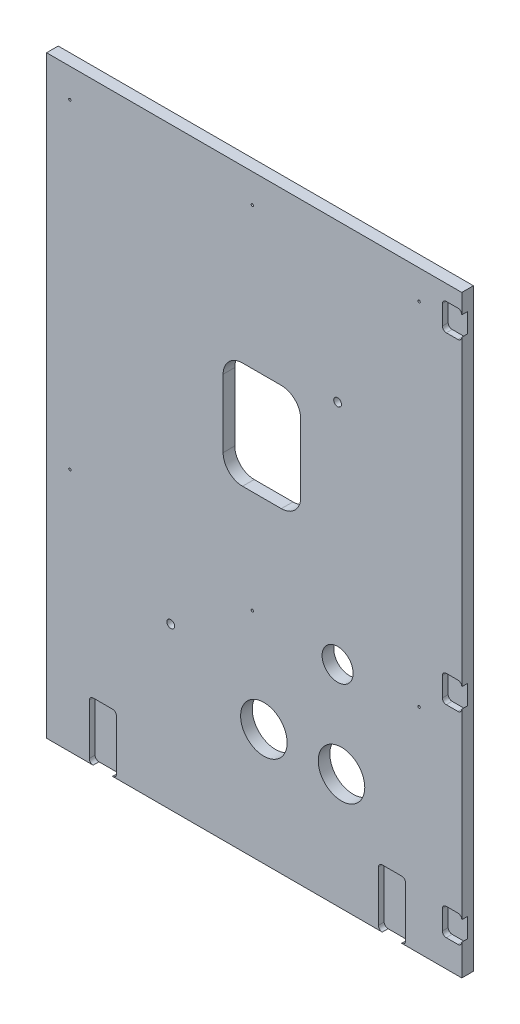
SolidWorks part; units mm, degrees
material "Фанера, берёза, ФСФ ВВ/С ГОСТ 3916.1-96"
ref_plane "Спереди" through (0, 0, 0) normal (0, 0, 1) x (1, 0, 0)
ref_plane "Сверху" through (0, 0, 0) normal (0, 1, 0) x (1, 0, 0)
ref_plane "Справа" through (0, 0, 0) normal (1, 0, 0) x (0, 0, -1)
sketch "Эскиз1" plane through (0, 0, 0) normal (0, 0, 1) x (1, 0, 0)
  line L1 (-535, -765) -> (535, -765)
  line L2 (-535, -765) -> (-535, 765)
  line L3 (-535, 765) -> (535, 765)
  line L4 (535, -765) -> (535, 765)
  line L5 (0, 765) -> (0, -765) construction
  line L6 (-535, 0) -> (535, 0) construction
  point P0 (0, 0)
  dimension "D1" = 1070
  dimension "D2" = 1530
extrude "Бобышка-Вытянуть1" add sketch "Эскиз1" along normal mid plane 30
sketch "Эскиз2" plane through (0, 0, 15) normal (0, 0, 1) x (1, 0, 0)
  line L0 (-535, 765) -> (-535, -765) construction
  line L1 (-30, 325) -> (70, 325)
  line L2 (-80, 275) -> (-80, 100)
  line L3 (-30, 50) -> (70, 50)
  line L4 (120, 275) -> (120, 100)
  line L5 (535, 765) -> (-535, 765) construction
  line L6 (535, -765) -> (535, 765) construction
  line L7 (-535, -765) -> (535, -765) construction
  arc A0 (70, 50) -> (120, 100) centre (70, 100) ccw
  arc A1 (-80, 100) -> (-30, 50) centre (-30, 100) ccw
  arc A2 (70, 325) -> (120, 275) centre (70, 275) cw
  arc A3 (-30, 325) -> (-80, 275) centre (-30, 275) ccw
  circle A4 centre (215, -225) radius 40
  circle A5 centre (225, -465) radius 60
  circle A6 centre (25, -465) radius 60
  circle A7 centre (215, 360) radius 10
  circle A8 centre (-215, -350) radius 10
  point P4 (20, 50)
  dimension "D5" = 50
  dimension "D6" = 80
  dimension "D9" = 120
  dimension "D13" = 20
  dimension "D1" = 275
  dimension "D2" = 200
  dimension "D3" = 455
  dimension "D4" = 440
  dimension "D7" = 320
  dimension "D8" = 540
  dimension "D10" = 310
  dimension "D11" = 300
  dimension "D12" = 510
  dimension "D14" = 405
  dimension "D15" = 320
  dimension "D16" = 320
  dimension "D17" = 415
extrude "Вырез-Вытянуть1" cut sketch "Эскиз2" against normal through all
sketch "Эскиз4" plane through (0, 0, 15) normal (0, 0, 1) x (1, 0, 0)
  line L0 (535, -765) -> (535, 765) construction
  line L1 (535, 765) -> (-535, 765) construction
  line L2 (-535, -765) -> (535, -765) construction
  line L3 (-535, 765) -> (-535, -765) construction
  point P0 (167.9177, -661.5146)
  line B0 (495, -105) -> (525, -105)
  line B1 (485, -115) -> (485, -165)
  line B2 (495, -175) -> (525, -175)
  line B3 (535, -115) -> (535, -165)
  arc B4 (525, -175) -> (535, -165) centre (525, -165) ccw
  arc B5 (485, -165) -> (495, -175) centre (495, -165) ccw
  arc B6 (525, -105) -> (535, -115) centre (525, -115) cw
  arc B7 (495, -105) -> (485, -115) centre (495, -115) ccw
  line B8 (495, -625) -> (525, -625)
  line B9 (485, -635) -> (485, -685)
  line B10 (495, -695) -> (525, -695)
  line B11 (535, -635) -> (535, -685)
  arc B12 (525, -695) -> (535, -685) centre (525, -685) ccw
  arc B13 (485, -685) -> (495, -695) centre (495, -685) ccw
  arc B14 (525, -625) -> (535, -635) centre (525, -635) cw
  arc B15 (495, -625) -> (485, -635) centre (495, -635) ccw
  line B16 (-390, -615) -> (-390, -765) construction
  line B17 (-415, -615) -> (-365, -615)
  line B18 (-425, -625) -> (-425, -755)
  line B19 (-415, -765) -> (-365, -765)
  line B20 (-355, -625) -> (-355, -755)
  arc B21 (-365, -765) -> (-355, -755) centre (-365, -755) ccw
  arc B22 (-425, -755) -> (-415, -765) centre (-415, -755) ccw
  arc B23 (-365, -615) -> (-355, -625) centre (-365, -625) cw
  arc B24 (-415, -615) -> (-425, -625) centre (-415, -625) ccw
  line B25 (495, 725) -> (525, 725)
  line B26 (485, 715) -> (485, 665)
  line B27 (495, 655) -> (525, 655)
  line B28 (535, 715) -> (535, 665)
  arc B29 (525, 655) -> (535, 665) centre (525, 665) ccw
  arc B30 (485, 665) -> (495, 655) centre (495, 665) ccw
  arc B31 (525, 725) -> (535, 715) centre (525, 715) cw
  arc B32 (495, 725) -> (485, 715) centre (495, 715) ccw
  line B33 (330, -615) -> (380, -615)
  line B34 (320, -625) -> (320, -755)
  line B35 (330, -765) -> (380, -765)
  line B36 (390, -625) -> (390, -755)
  arc B37 (380, -765) -> (390, -755) centre (380, -755) ccw
  arc B38 (320, -755) -> (330, -765) centre (330, -755) ccw
  arc B39 (380, -615) -> (390, -625) centre (380, -625) cw
  arc B40 (330, -615) -> (320, -625) centre (330, -625) ccw
  dimension "D1" = 40
  dimension "D2" = 870
  dimension "D3" = 70
  dimension "D4" = 110
  dimension "D5" = 145
sketch_block_instance "Блок1-2"
sketch_block "Блок1" parameters "D3"=10, "D1"=70, "D2"=50
sketch_block_instance "Блок1-3"
sketch_block "Блок1" parameters "D3"=10, "D1"=70, "D2"=50
sketch_block_instance "Блок3-1"
sketch_block "Блок3" parameters "D2"=10, "D1"=70, "D3"=50
sketch_block_instance "Блок1-1"
sketch_block "Блок1" parameters "D3"=10, "D1"=70, "D2"=50
sketch_block_instance "Блок3-2"
extrude "Вырез-Вытянуть2" cut sketch "Эскиз4" against normal blind 15
sketch "Эскиз5" plane through (0, 0, 15) normal (0, 0, 1) x (1, 0, 0)
  line L0 (535, 765) -> (-535, 765) construction
  line L1 (-535, 765) -> (-535, -765) construction
  point P0 (-492.6091, 591.725)
  circle B0 centre (-475, 690) radius 3
  circle B1 centre (-5, 690) radius 3
  circle B2 centre (425, 690) radius 3
  circle B3 centre (-475, -135) radius 3
  circle B4 centre (-5, -215) radius 3
  circle B5 centre (425, -215) radius 3
  dimension "D1" = 75
  dimension "D2" = 60
  dimension "D3" = 470
  dimension "D4" = 430
  dimension "D5" = 825
  dimension "D6" = 905
sketch_block_instance "Блок4-1"
sketch_block "Блок4" parameters "D1"=6
sketch_block_instance "Блок4-2"
sketch_block_instance "Блок4-3"
sketch_block_instance "Блок4-4"
sketch_block_instance "Блок4-5"
sketch_block_instance "Блок4-6"
extrude "Вырез-Вытянуть3" cut sketch "Эскиз5" against normal through all
equation "\"ширина 1-я панель\"=1145"
equation "\"длина панелей\"=1530"
equation "\"толщина дсп\"=30"
equation "\"ширина 2-я панель\"=1070"
equation "\"D2@Эскиз1\"=\"длина панелей\""
equation "\"D1@Эскиз1\"=\"ширина 2-я панель\""
